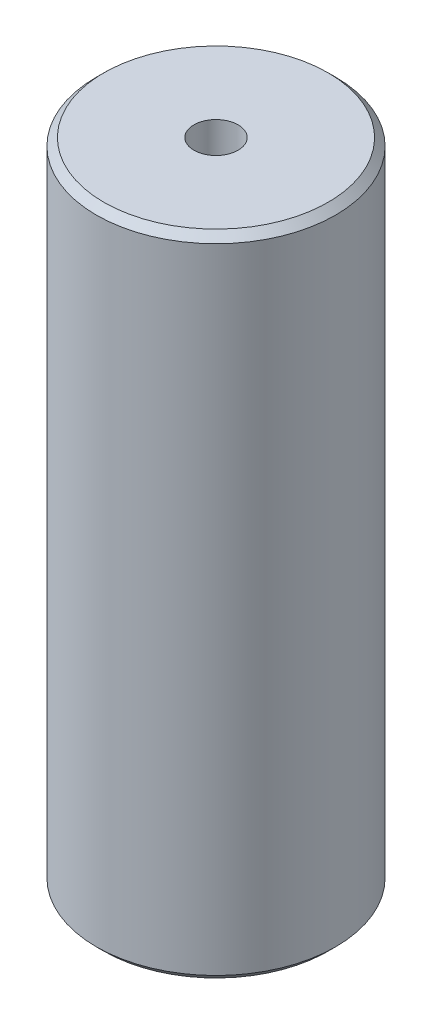
SolidWorks part; units mm, degrees
ref_plane "Front Plane" through (0, 0, 0) normal (0, 0, 1) x (1, 0, 0)
ref_plane "Top Plane" through (0, 0, 0) normal (0, 1, 0) x (1, 0, 0)
ref_plane "Right Plane" through (0, 0, 0) normal (1, 0, 0) x (0, 0, -1)
sketch "Sketch1" plane through (0, 0, 0) normal (0, 1, 0) x (1, 0, 0)
  circle A0 centre (0, 0) radius 5
  dimension "SHAFT_OD" = 10
extrude "Boss-Extrude1" add sketch "Sketch1" along normal blind 27.1202
sketch "Sketch2" plane through (0, 0, 0) normal (0, 1, 0) x (1, 0, 0)
  circle A0 centre (0, 0) radius 0.9229
  dimension "BORE_D" = 1.8459
extrude "Cut-Extrude1" cut sketch "Sketch2" along normal through all
chamfer "Chamfer1" distance 0.3104 angle 45 2 edges at (0, 27.1202, 5) (0, 0, 5)
